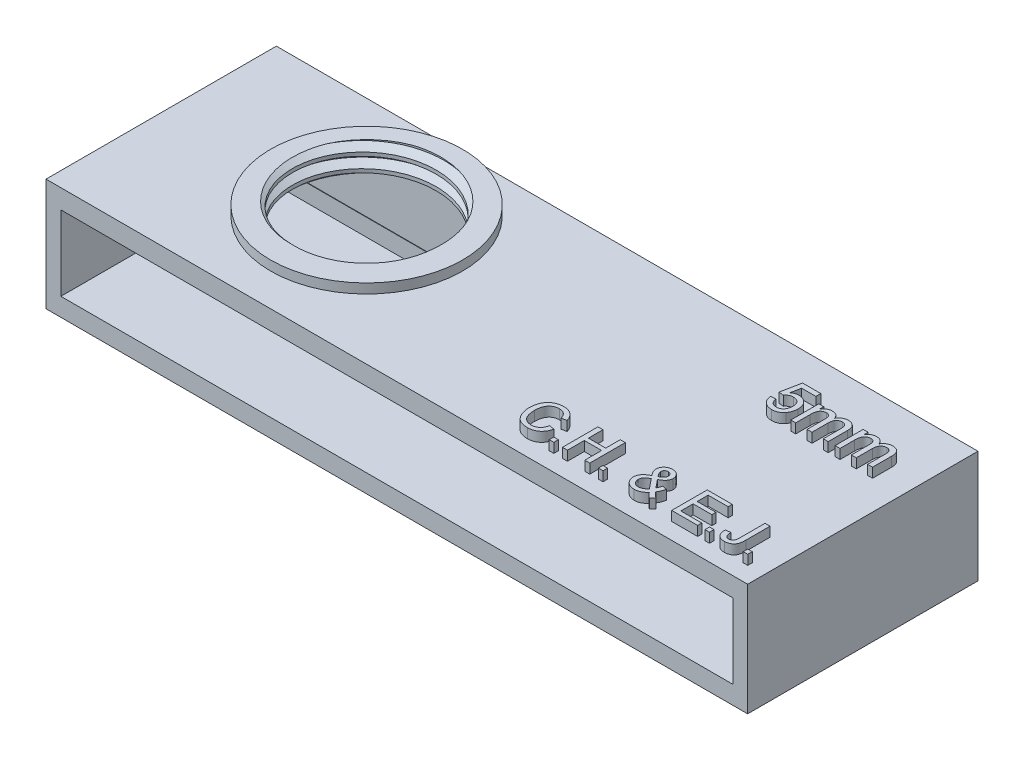
SolidWorks part; units mm, degrees
ref_plane "Ebene vorne" through (0, 0, 0) normal (0, 0, 1) x (1, 0, 0)
ref_plane "Ebene oben" through (0, 0, 0) normal (0, 1, 0) x (1, 0, 0)
ref_plane "Ebene rechts" through (0, 0, 0) normal (1, 0, 0) x (0, 0, -1)
sketch "Skizze1" plane through (0, 0, 0) normal (0, 1, 0) x (1, 0, 0)
  line L1 (-46.4165, 18.2033) -> (26.6835, 18.2033)
  line L2 (-46.4165, 18.2033) -> (-46.4165, -3.7967)
  line L3 (-46.4165, -3.7967) -> (26.6835, -3.7967)
  line L4 (26.6835, 18.2033) -> (26.6835, -3.7967)
  dimension "D1" = 73.1
  dimension "D2" = 22
extrude "Basis" add sketch "Skizze1" along normal blind 11.7
ref_plane "Ebene seitlich Handyschlitz" through (0, 0, 3.7967) normal (0, 0, 1) x (1, 0, 0)
sketch "Skizze2" plane through (0, 0, 3.7967) normal (0, 0, 1) x (1, 0, 0)
  line L1 (-44.8665, 9.7) -> (25.1335, 9.7)
  line L2 (-44.8665, 9.7) -> (-44.8665, 1.9)
  line L3 (-44.8665, 1.9) -> (25.1335, 1.9)
  line L4 (25.1335, 9.7) -> (25.1335, 1.9)
  line L5 (-46.4165, 11.7) -> (-46.4165, 0) construction
  line L6 (-46.4165, 11.7) -> (26.6835, 11.7) construction
  dimension "D1" = 70
  dimension "D2" = 7.8
  dimension "D3" = 2
  dimension "D4" = 1.55
extrude "Handyschlitz" cut sketch "Skizze2" against normal blind 21.25
ref_plane "Ebene oben auf Basis für Zylinder" through (0, 11.7, 0) normal (0, 1, 0) x (1, 0, 0)
sketch "Skizze3" plane through (0, 11.7, 0) normal (0, 1, 0) x (1, 0, 0)
  line L0 (-46.4165, 18.2033) -> (-46.4165, -3.7967) construction
  line L1 (26.6835, 18.2033) -> (-46.4165, 18.2033) construction
  circle A0 centre (-26.4165, 9.6033) radius 6.3
  dimension "D1" = 20
  dimension "D2" = 8.6
extrude "Zylinder" add sketch "Skizze3" along normal blind 1
ref_plane "Ebene oben auf Zylinder" through (0, 12.7, 0) normal (0, 1, 0) x (1, 0, 0)
sketch "Skizze6" plane through (0, 11.7, 0) normal (0, 1, 0) x (1, 0, 0)
  circle A0 centre (-26.4165, 9.6033) radius 10
  dimension "D1" = 20
extrude "Aufsatz-Linear austragen1" add sketch "Skizze6" along normal blind 1 contours A0
sketch "Skizze8" plane through (0, 12.7, 0) normal (0, 1, 0) x (1, 0, 0)
  circle A0 centre (-26.4165, 9.6033) radius 8.3
  dimension "D1" = 16.6
extrude "Schnitt-Linear austragen2" cut sketch "Skizze8" against normal blind 3
ref_plane "Ebene3" through (0, 9.7, 0) normal (0, -1, 0) x (-1, 0, 0)
sketch "Skizze12" plane through (0, 12.7, 0) normal (0, 1, 0) x (1, 0, 0)
  circle A0 centre (-26.4165, 9.6033) radius 15
  dimension "D1" = 30
thread "Gewinde2" pitch 1.5 method extrude profile "Gewindeprofil2" start angle 0, offset 1.6, length 4, pitch 1.5, diameter 16.6
ref_plane "Ebene5" through (-34.7165, 14.3, -9.6033) normal (0, 0, 1) x (-1, 0, 0)
sketch "Gewindeprofil2" plane through (-34.7165, 14.3, -9.6033) normal (0, 0, 1) x (-1, 0, 0)
  line L0 (0, 0) -> (0, 1.5) construction
  line L11 (0, 0) -> (0, 1.3125)
  line L12 (0, 1.3125) -> (-0.8119, 0.8437)
  line L13 (-0.8119, 0.8437) -> (-0.8119, 0.4687)
  line L15 (-0.8119, 0.4687) -> (0, 0)
  line L17 (-0.8119, 0.6562) -> (0, 0.6562) construction
  point P2 (0, 0)
  dimension "Pitch" = 1.5
  dimension "Profile_Angle" = 60
  dimension "Profile_Land" = 0.375
  dimension "Profile_Height" = 0.8119
extrude "Schnitt-Linear austragen5" cut sketch "Skizze12" along normal blind 6 contours A0
sketch "Skizze17" plane through (0, 9.7, 0) normal (0, -1, 0) x (-1, 0, 0)
  line L1 (13.3814, 0) -> (43.6823, 0)
  line L2 (13.3814, 0) -> (13.3814, 17.5)
  line L3 (13.3814, 17.5) -> (43.6823, 17.5)
  line L4 (43.6823, 0) -> (43.6823, 17.5)
  dimension "D1" = 17.5
extrude "Schnitt-Linear austragen7" cut sketch "Skizze17" along normal blind 6
ref_plane "Ebene für Logo" through (0, 0, 0) normal (0, -1, 0) x (-1, 0, 0)
sketch "Skizze24" plane through (0, 0, 0) normal (0, -1, 0) x (-1, 0, 0)
  line L1 (33.7615, 1.4341) -> (32.0294, -1.5659)
  line L2 (32.0294, -1.5659) -> (35.4935, -1.5659)
  line L3 (35.4935, -1.5659) -> (33.7615, 1.4341)
  line L4 (35.9478, -1.5381) -> (37.6798, 1.4619)
  line L5 (37.6798, 1.4619) -> (34.2157, 1.4619)
  line L6 (34.2157, 1.4619) -> (35.9478, -1.5381)
  line L7 (38.0931, 1.4341) -> (36.3611, -1.5659)
  line L8 (36.3611, -1.5659) -> (39.8252, -1.5659)
  line L9 (39.8252, -1.5659) -> (38.0931, 1.4341)
  line L10 (40.2382, -1.5381) -> (41.9702, 1.4619)
  line L11 (41.9702, 1.4619) -> (38.5061, 1.4619)
  line L12 (38.5061, 1.4619) -> (40.2382, -1.5381)
  line L13 (42.3422, 1.4341) -> (40.6101, -1.5659)
  line L14 (40.6101, -1.5659) -> (44.0742, -1.5659)
  line L15 (44.0742, -1.5659) -> (42.3422, 1.4341)
  line L16 (35.9475, 4.8546) -> (34.2154, 1.8546)
  line L17 (34.2154, 1.8546) -> (37.6795, 1.8546)
  line L18 (37.6795, 1.8546) -> (35.9475, 4.8546)
  line L19 (38.1338, 1.9341) -> (39.8658, 4.9341)
  line L20 (39.8658, 4.9341) -> (36.4017, 4.9341)
  line L21 (36.4017, 4.9341) -> (38.1338, 1.9341)
  line L22 (40.2791, 4.8546) -> (38.547, 1.8546)
  line L23 (38.547, 1.8546) -> (42.0111, 1.8546)
  line L24 (42.0111, 1.8546) -> (40.2791, 4.8546)
  line L28 (38.1338, 8.3316) -> (36.4017, 5.3316)
  line L29 (36.4017, 5.3316) -> (39.8658, 5.3316)
  line L30 (39.8658, 5.3316) -> (38.1338, 8.3316)
  circle A0 centre (33.7615, -0.5659) radius 1 construction
  circle A1 centre (35.9478, 0.4619) radius 1 construction
  circle A2 centre (38.0931, -0.5659) radius 1 construction
  circle A3 centre (40.2382, 0.4619) radius 1 construction
  circle A4 centre (42.3422, -0.5659) radius 1 construction
  circle A5 centre (35.9475, 2.8546) radius 1 construction
  circle A6 centre (38.1338, 3.9341) radius 1 construction
  circle A7 centre (40.2791, 2.8546) radius 1 construction
  circle A8 centre (38.1338, 6.3316) radius 1 construction
sketch "Skizze25" plane through (0, 0, 0) normal (0, -1, 0) x (-1, 0, 0)
  text T0 "EAH JENA         " font "Arial" height 3.5
extrude "EAH Jena" add sketch "Skizze25" along normal blind 1
extrude "LOGO" add sketch "Skizze24" along normal blind 1
ref_plane "Ebene für Schrift oben" through (0, 11.7, 0) normal (0, 1, 0) x (1, 0, 0)
sketch "Skizze26" plane through (0, 11.7, 0) normal (0, 1, 0) x (1, 0, 0)
  text T0 "C.H. & E.J." font "Arial" height 3.7
extrude "C.H. & E.J." add sketch "Skizze26" along normal blind 1
sketch "Skizze27" plane through (0, 11.7, 0) normal (0, 1, 0) x (1, 0, 0)
  text T0 "5mm" font "Arial" height 4
extrude "5mm" add sketch "Skizze27" along normal blind 1
sketch "Skizze29" plane through (0, 0, -18.2033) normal (0, 0, -1) x (-1, 0, 0)
  line L1 (46.4165, 0) -> (-26.6835, 0)
  line L2 (46.4165, 0) -> (46.4165, 11.7)
  line L3 (46.4165, 11.7) -> (-26.6835, 11.7)
  line L4 (-26.6835, 0) -> (-26.6835, 11.7)
extrude "Aufsatz-Linear austragen2" add sketch "Skizze29" along normal blind 2
